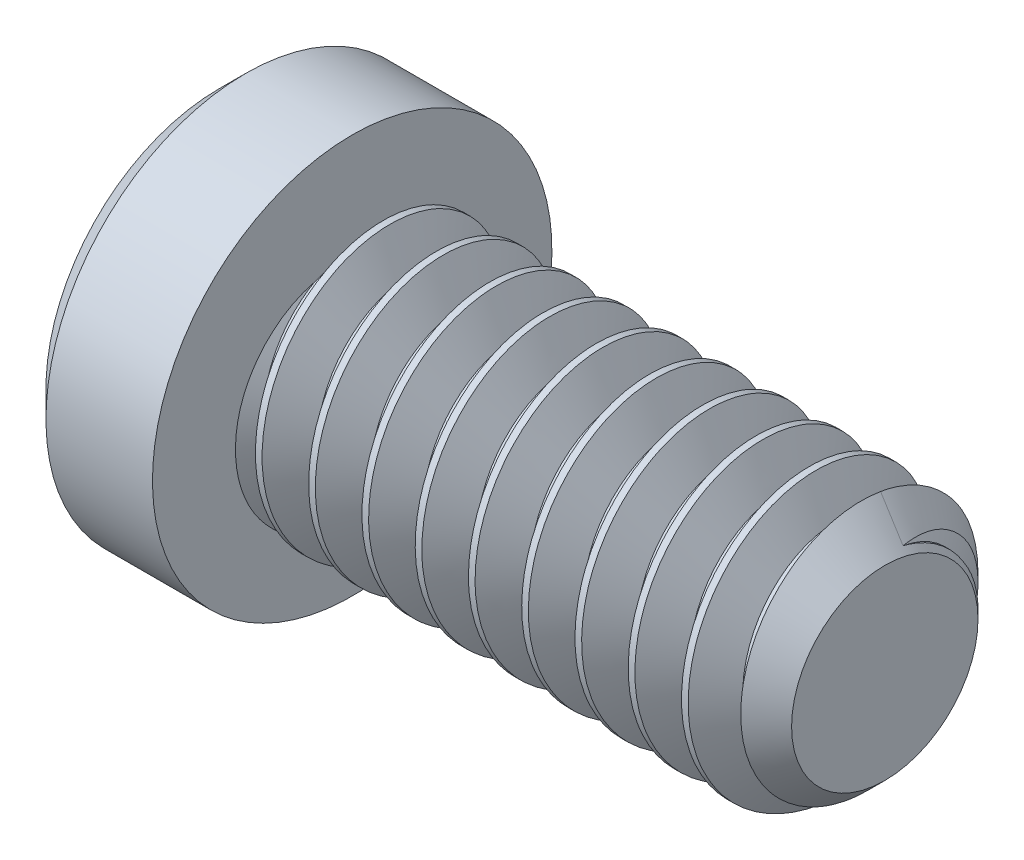
SolidWorks part; units mm, degrees
ref_plane "Front Plane" through (0, 0, 0) normal (0, 0, 1) x (1, 0, 0)
ref_plane "Top Plane" through (0, 0, 0) normal (0, 1, 0) x (1, 0, 0)
ref_plane "Right Plane" through (0, 0, 0) normal (1, 0, 0) x (0, 0, -1)
sketch "Sketch1" plane through (0, 0, 0) normal (0, 0, 1) x (1, 0, 0)
  line L0 (6.35, 0) -> (-6.35, 0) construction
  line L1 (6.35, 3.175) -> (6.35, -3.175) construction
  line L2 (-6.35, 4.7625) -> (-6.35, -4.7625) construction
  line L3 (-6.35, 4.7625) -> (-8.89, 4.7625) construction
  line L4 (-8.89, 4.7625) -> (-9.525, 4.1275) construction
  line L5 (-9.525, 4.1275) -> (-9.525, -4.1275) construction
  line L6 (-9.525, -4.1275) -> (-8.89, -4.7625) construction
  line L7 (-8.89, -4.7625) -> (-6.35, -4.7625) construction
  point P7 (-7.1374, 0)
  point P12 (1.27, -3.175)
  dimension "D1" = 45
  dimension "D2" = 5.08
  dimension "Dec." = 6.35
  dimension "Length" = 12.7
  dimension "Head Dia" = 9.525
  dimension "Head Height" = 3.175
  dimension "Hex Depth" = 2.3876
  dimension "Chamfer" = 0.635
ref_plane "Plane1" through (6.35, 0, 0) normal (1, 0, 0) x (0, 0, -1)
ref_plane "Plane2" through (-9.525, 0, 0) normal (1, 0, 0) x (0, 0, -1)
sketch "Sketch2" plane through (6.35, 0, 0) normal (1, 0, 0) x (0, 0, -1)
  circle A0 centre (0, 0) radius 3.175
extrude "Boss-Extrude1" add sketch "Sketch2" against normal up to vertex (12.7 mm away) up to point (-6.35, 0, 0)
sketch "Sketch3" plane through (6.35, 0, 0) normal (1, 0, 0) x (0, 0, -1)
  circle A0 centre (0, 0) radius 3.175 construction
  circle A1 centre (0, 0) radius 3.175
curve "Helix/Spiral1" pitch 1.27 height 13.97 radius 3.175 centre (6.35, 0, 0) axis (-1, 0, 0) start towards (0, 1, 0) parameters "Pitch"=1.27
chamfer "Chamfer1" distance 0.9525 angle 45 1 edges at (6.35, 0, -3.175)
sketch "Sketch5" plane through (0, 0, 0) normal (0, 0, 1) x (1, 0, 0)
  line L0 (5.7944, 3.175) -> (6.9056, 3.175)
  line L1 (6.9056, 3.175) -> (6.4294, 2.3501)
  line L2 (6.4294, 2.3501) -> (6.2706, 2.3501)
  line L3 (6.2706, 2.3501) -> (5.7944, 3.175)
  line L4 (6.35, 2.3501) -> (6.35, 3.175) construction
  line L5 (6.0325, 2.7626) -> (6.6675, 2.7626) construction
  dimension "D1" = 60
  dimension "D2" = 0.635
  dimension "D3" = 0.1588
sweep "Cut-Sweep1" cut profiles "Sketch5" path "Helix/Spiral1"
sketch "Sketch4" plane through (-9.525, 0, 0) normal (1, 0, 0) x (0, 0, -1)
  line L0 (-4.7625, 0.7937) -> (4.7625, 0.7937) construction
  line L1 (0, 1.8331) -> (-1.5875, 0.9165)
  line L2 (-1.5875, 0.9165) -> (-1.5875, -0.9165)
  line L3 (-1.5875, -0.9165) -> (0, -1.8331)
  line L4 (0, -1.8331) -> (1.5875, -0.9165)
  line L5 (1.5875, -0.9165) -> (1.5875, 0.9165)
  line L6 (1.5875, 0.9165) -> (0, 1.8331)
  line L7 (0, 0) -> (0, 0.7937) construction
  circle A0 centre (0, 0) radius 1.5875 construction
  dimension "D1" = 9.525
  dimension "Hex Size" = 3.175
  dimension "D2" = 0.7937
sketch "Sketch6" plane through (0, 0, 0) normal (0, 0, 1) x (1, 0, 0)
  line L0 (-8.89, 4.7625) -> (-9.525, 4.1275) construction
  line L1 (-6.35, 4.7625) -> (-8.89, 4.7625) construction
  line L2 (-6.35, 4.7625) -> (-6.35, -4.7625) construction
  line L3 (-9.525, 4.1275) -> (-9.525, -4.1275) construction
  line L4 (-8.89, 4.7625) -> (-9.525, 4.1275)
  line L5 (-6.35, 4.7625) -> (-8.89, 4.7625)
  line L6 (-6.35, 4.7625) -> (-6.35, 0)
  line L7 (-9.525, 4.1275) -> (-9.525, 0)
  line L8 (-6.35, 0) -> (-9.525, 0) construction
  line L9 (-6.35, 0) -> (-9.525, 0)
revolve "Revolve1" add sketch "Sketch6" angle 360 about L8
extrude "Cut-Extrude1" cut sketch "Sketch4" along normal up to vertex (2.3876 mm away) up to point (-7.1374, 0, 0)
sketch "Sketch8" plane through (-9.525, 0, 0) normal (-1, 0, 0) x (0, 0, 1)
  circle A1 centre (0, 0) radius 1.8331
extrude "Cut-Extrude2" cut sketch "Sketch8" against normal through all draft 45
equation "\"D3@Helix/Spiral1\" = \"Length@Sketch1\"+\"Pitch@Helix/Spiral1\""
equation "\"D3@Sketch5\" = \"Pitch@Helix/Spiral1\"*.125"
equation "\"D2@Sketch5\" = \"Pitch@Helix/Spiral1\"*.50"
equation "\"D1@Chamfer1\" = \"Pitch@Helix/Spiral1\"*.75"
equation "\"D2@Sketch1\" = \"Pitch@Helix/Spiral1\"*4"
equation "\"D1@Sketch4\" = \"Head Dia@Sketch1\""
